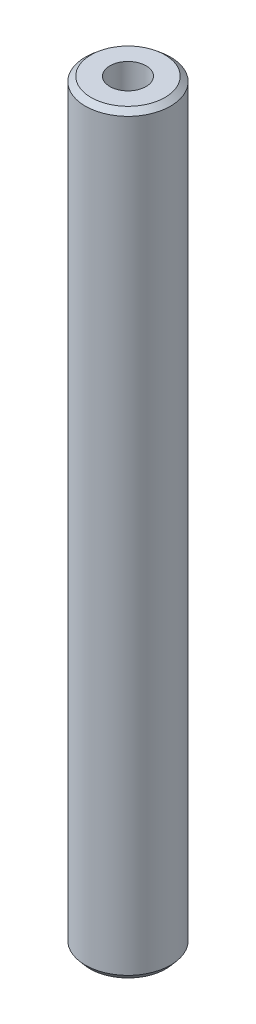
SolidWorks part; units mm, degrees
ref_plane "Front Plane" through (0, 0, 0) normal (0, 0, 1) x (1, 0, 0)
ref_plane "Top Plane" through (0, 0, 0) normal (0, 1, 0) x (1, 0, 0)
ref_plane "Right Plane" through (0, 0, 0) normal (1, 0, 0) x (0, 0, -1)
sketch "Sketch1" plane through (0, 0, 0) normal (0, 1, 0) x (1, 0, 0)
  circle A0 centre (0, 0) radius 5
  dimension "SHAFT_OD" = 10
extrude "Boss-Extrude1" add sketch "Sketch1" along normal blind 88.5992
sketch "Sketch2" plane through (0, 0, 0) normal (0, 1, 0) x (1, 0, 0)
  circle A0 centre (0, 0) radius 2.1211
  dimension "BORE_D" = 4.2422
extrude "Cut-Extrude1" cut sketch "Sketch2" along normal through all
chamfer "Chamfer1" distance 0.5533 angle 50.029 2 edges at (0, 88.5992, 5) (0, 0, 5) first distance on face at (0, 88.5992, 5) first distance on face at (0, 0, 2.1211)
